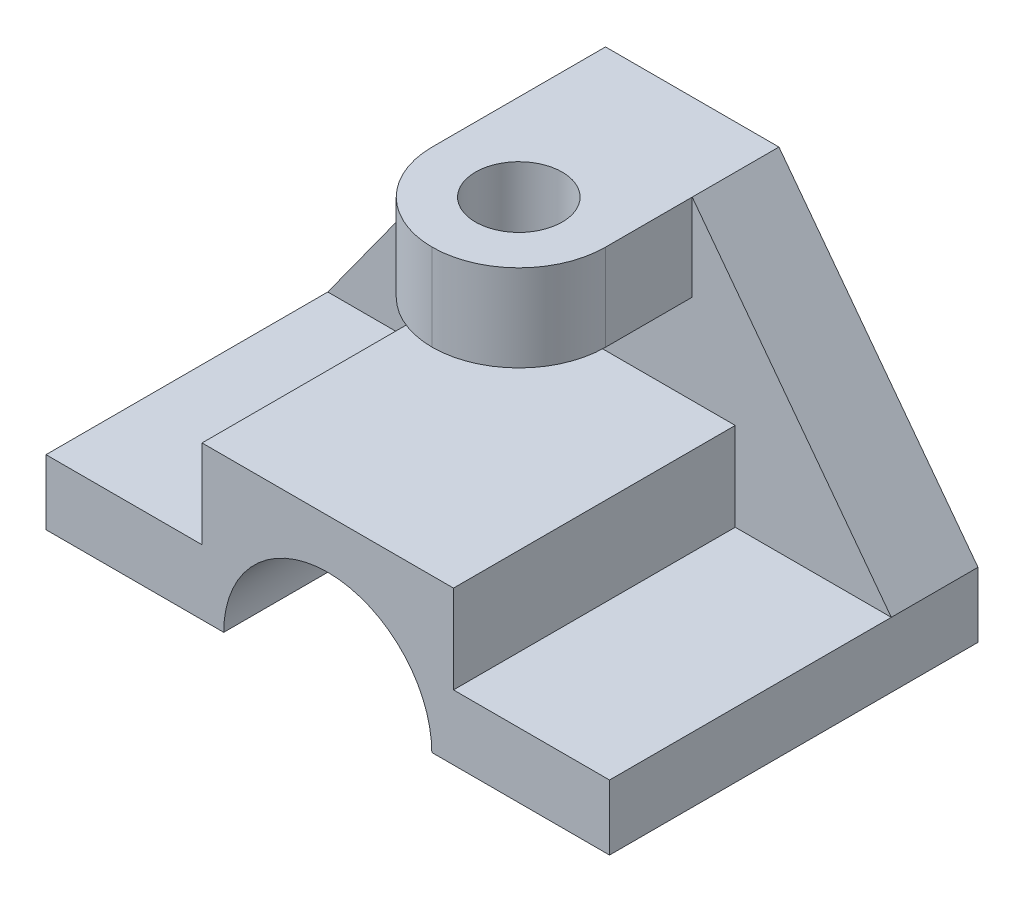
SolidWorks part; units mm, degrees
ref_plane "정면" through (0, 0, 0) normal (0, 0, 1) x (1, 0, 0)
ref_plane "윗면" through (0, 0, 0) normal (0, 1, 0) x (1, 0, 0)
ref_plane "우측면" through (0, 0, 0) normal (1, 0, 0) x (0, 0, -1)
sketch "스케치1" plane through (0, 0, 0) normal (0, 0, 1) x (1, 0, 0)
  line L0 (-24, -15.1996) -> (-65, -15.1996)
  line L1 (-65, -15.1996) -> (-65, -0.1996)
  line L2 (-65, -0.1996) -> (-29, -0.1996)
  line L3 (-29, -0.1996) -> (-29, 20.1426)
  line L4 (-29, 20.1426) -> (29, 20.1426)
  line L5 (29, 20.1426) -> (29, -0.1996)
  line L6 (29, -0.1996) -> (65, -0.1996)
  line L7 (65, -0.1996) -> (65, -15.1996)
  line L8 (65, -15.1996) -> (24, -15.1996)
  arc A0 (24, -15.1996) -> (-24, -15.1996) centre (0, -15.1996) ccw
  point P11 (0, 20.1426)
  point P12 (-27.9948, -15.1996)
  point P13 (0, 0)
  point P14 (0, 0)
  point P15 (0, 0)
  point P16 (-24.9656, -15.1996)
  point P17 (29.5908, -19.6483)
  point P18 (24.9656, -15.1996)
  dimension "D2" = 24
  dimension "D1" = 130
  dimension "D3" = 58
  dimension "D4" = 15
extrude "보스-돌출2" add sketch "스케치1" along normal blind 85
sketch "스케치4" plane through (0, 0, 0) normal (0, 0, -1) x (-1, 0, 0)
  line L0 (-65, -0.1996) -> (-29, -0.1996)
  line L1 (-29, -0.1996) -> (-29, 20.1426)
  line L2 (-29, 20.1426) -> (29, 20.1426)
  line L3 (29, 20.1426) -> (29, -0.1996)
  line L4 (29, -0.1996) -> (65, -0.1996)
  line L5 (65, -0.1996) -> (20.9232, 60.8004)
  line L6 (20.9232, 60.8004) -> (-19.0768, 60.8004)
  line L7 (-19.0768, 60.8004) -> (-65, -0.1996)
  line L8 (65, -15.1996) -> (24, -15.1996) construction
  dimension "D1" = 40
  dimension "D2" = 76
extrude "보스-돌출3" add sketch "스케치4" against normal blind 20
sketch "스케치5" plane through (0, 0, 20) normal (0, 0, 1) x (1, 0, 0)
  line L0 (-20.9232, 60.8004) -> (19.0768, 60.8004) construction
  line L1 (-20.9232, 60.8004) -> (19.0768, 60.8004)
  line L2 (-20.9232, 60.8004) -> (-20.9232, 40.8004)
  line L3 (-20.9232, 40.8004) -> (19.0768, 40.8004)
  line L4 (19.0768, 60.8004) -> (19.0768, 40.8004)
  dimension "D1" = 20
  dimension "D2" = 40
extrude "보스-돌출4" add sketch "스케치5" along normal blind 40
fillet "필렛1" radius 20 2 edges at (-20.9232, 50.8004, 60) (19.0768, 50.8004, 60)
sketch "스케치6" plane through (0, 60.8004, 0) normal (0, 1, 0) x (1, 0, 0)
  circle A0 centre (-0.9232, -40) radius 10
  dimension "D1" = 20
extrude "컷-돌출1" cut sketch "스케치6" against normal blind 20 contours A0
